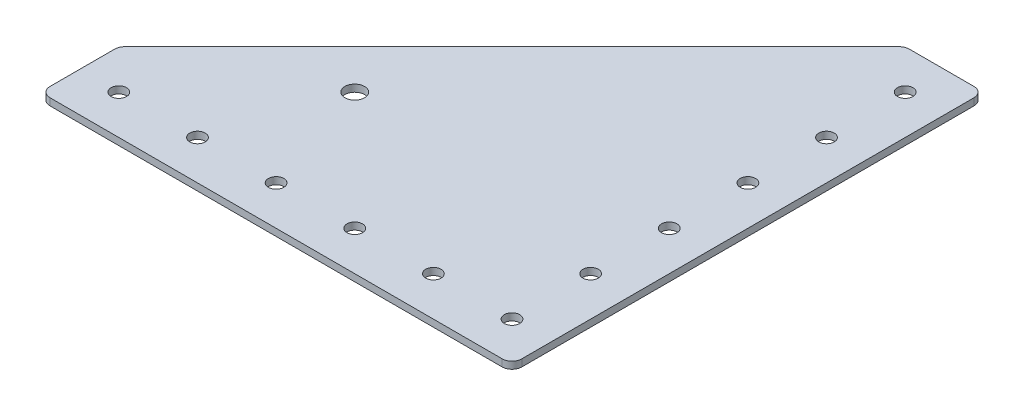
SolidWorks part; units mm, degrees
material "6061-T6 (SS)"
ref_plane "Front Plane" through (0, 0, 0) normal (0, 0, 1) x (1, 0, 0)
ref_plane "Top Plane" through (0, 0, 0) normal (0, 1, 0) x (1, 0, 0)
ref_plane "Right Plane" through (0, 0, 0) normal (1, 0, 0) x (0, 0, -1)
sketch "Sketch1" plane through (0, 0, 0) normal (0, 1, 0) x (1, 0, 0)
  line L0 (0, 0) -> (0, 152.4)
  line L1 (0, 152.4) -> (-25.4, 152.4)
  line L2 (-25.4, 152.4) -> (-152.4, 25.4)
  line L3 (-152.4, 25.4) -> (-152.4, 0)
  line L4 (-152.4, 0) -> (0, 0)
  circle A0 centre (-12.7, 12.7) radius 2.4892
  circle A1 centre (-38.1, 12.7) radius 2.4892
  circle A2 centre (-63.5, 12.7) radius 2.4892
  circle A3 centre (-88.9, 12.7) radius 2.4892
  circle A4 centre (-114.3, 12.7) radius 2.4892
  circle A5 centre (-12.7, 38.1) radius 2.4892
  circle A6 centre (-12.7, 63.5) radius 2.4892
  circle A7 centre (-12.7, 88.9) radius 2.4892
  circle A8 centre (-12.7, 114.3) radius 2.4892
  circle A9 centre (-139.7, 12.7) radius 2.4892
  circle A13 centre (-12.7, 139.7) radius 2.4892
  circle A17 centre (-101.6, 50.8) radius 3.175
  dimension "D4" = 12.7
  dimension "D5" = 12.7
  dimension "D11" = 6.35
  dimension "D12" = 4.9784
  dimension "D1" = 152.4
  dimension "D2" = 25.4
  dimension "D3" = 152.4
  dimension "D8" = 101.6
  dimension "D9" = 50.8
  dimension "D10" = 25.4
  dimension "D6" = 6
  dimension "D7" = 6
extrude "Boss-Extrude2" add sketch "Sketch1" along normal mid plane 2.286
fillet "Fillet1" radius 3.175 2 edges at (0, 0, 0) (-152.4, 0, 0)
fillet "Fillet2" radius 3.175 3 edges at (-152.4, 0, -25.4) (-25.4, 0, -152.4) (0, 0, -152.4)
sketch "Sketch2" plane through (0, 1.143, 0) normal (0, 1, 0) x (1, 0, 0)
  line L1 (0, 0) -> (-152.4, 0)
  line L2 (0, 0) -> (0, 152.4)
  line L3 (0, 152.4) -> (-152.4, 152.4)
  line L4 (-152.4, 0) -> (-152.4, 152.4)
  dimension "D1" = 152.4
  dimension "D2" = 152.4
  dimension "D3" = 152.4
